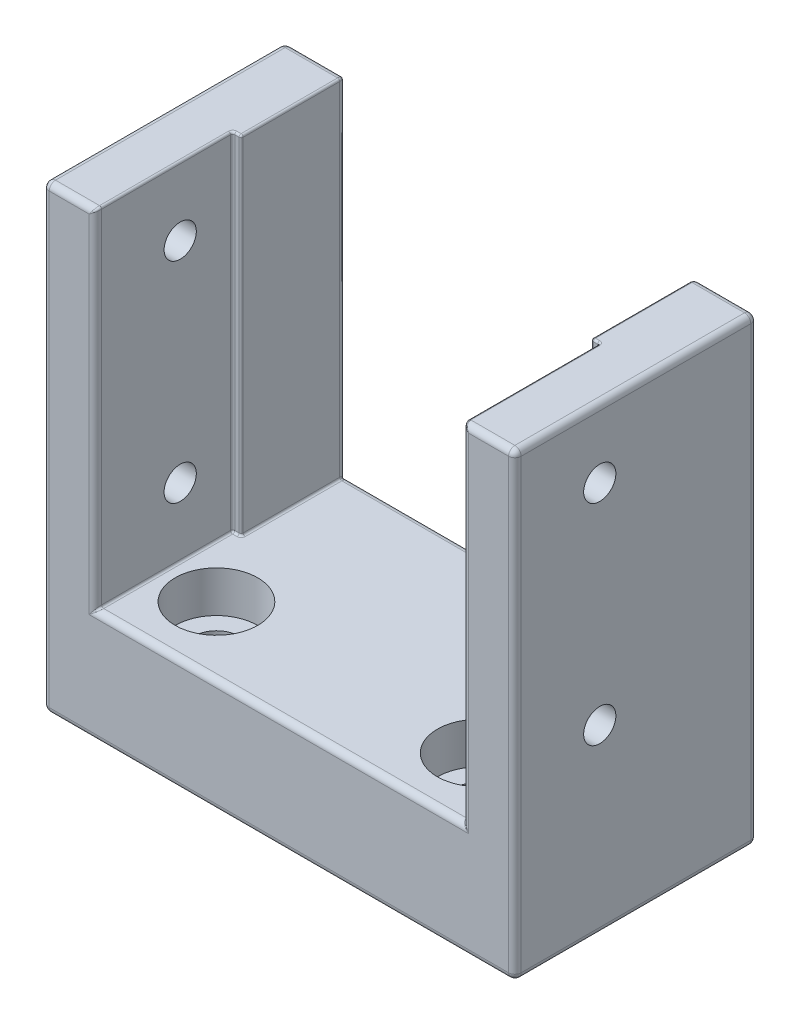
SolidWorks part; units mm, degrees
material "PLA"
ref_plane "Front Plane" through (0, 0, 0) normal (0, 0, 1) x (1, 0, 0)
ref_plane "Top Plane" through (0, 0, 0) normal (0, 1, 0) x (1, 0, 0)
ref_plane "Right Plane" through (0, 0, 0) normal (1, 0, 0) x (0, 0, -1)
sketch "Sketch1" plane through (0, 0, 0) normal (0, 1, 0) x (1, 0, 0)
  line L1 (-22.225, 14.6625) -> (22.225, 14.6625)
  line L2 (-22.225, 14.6625) -> (-22.225, -14.6625)
  line L3 (-22.225, -14.6625) -> (22.225, -14.6625)
  line L4 (22.225, 14.6625) -> (22.225, -14.6625)
  point P4 (0, -14.6625)
  point P6 (-22.225, 0)
  dimension "D1" = 29.325
  dimension "D2" = 44.45
extrude "Boss-Extrude1" add sketch "Sketch1" against normal blind 13.685
sketch "Sketch2" plane through (22.225, 0, 0) normal (1, 0, 0) x (0, 0, -1)
  line L0 (14.6625, -13.685) -> (14.6625, 0) construction
  line L1 (-14.6625, -13.685) -> (14.6625, -13.685)
  line L2 (-14.6625, -13.685) -> (-14.6625, 42)
  line L3 (-14.6625, 42) -> (14.6625, 42)
  line L4 (14.6625, -13.685) -> (14.6625, 42)
  dimension "D1" = 55.685
extrude "Boss-Extrude2" add sketch "Sketch2" along normal blind 6.35
hole_wizard "M3.5 Clearance Hole1" positions "Sketch5" profile "Sketch6" hole size "M3.5" standard "ANSI Metric" end condition through all
sketch "Sketch5" plane through (28.575, 0, 0) normal (1, 0, 0) x (0, 0, -1)
  line L1 (14.6625, 42) -> (-14.6625, 42) construction
  line L2 (-14.6625, 42) -> (-14.6625, -13.685) construction
  point P0 (-4.3875, 33.7)
  point P2 (-4.3875, 8.3)
  dimension "D1" = 10.275
  dimension "D2" = 8.3
  dimension "D3" = 25.4
sketch "Sketch6" plane through (28.575, 33.7, 4.3875) normal (0, 1, 0) x (0, 0, -1)
  line L0 (0, 0) -> (0, 50.8)
  line L1 (0, 50.8) -> (1.95, 50.8)
  line L2 (1.95, 50.8) -> (1.95, 0)
  line L5 (1.95, 0) -> (0, 0)
  line L11 (0, -6.35) -> (0, 107.95) construction
  dimension "Thru Hole Dia." = 3.9
  dimension "Thru Hole Depth" = 50.8
mirror "Mirror1" about plane through (0, 0, 0) normal (1, 0, 0) of "Boss-Extrude2", "M3.5 Clearance Hole1"
sketch "Sketch8" plane through (22.225, 0, 0) normal (-1, 0, 0) x (0, 0, 1)
  line L0 (-14.6625, 42) -> (14.6625, 42) construction
  line L1 (-14.6625, 0) -> (-1.9625, 0)
  line L2 (-14.6625, 0) -> (-14.6625, 42)
  line L3 (-14.6625, 42) -> (-1.9625, 42)
  line L4 (-1.9625, 0) -> (-1.9625, 42)
  dimension "D1" = 12.7
extrude "Boss-Extrude6" add sketch "Sketch8" along normal blind 1.025
mirror "Mirror2" about plane through (0, 0, 0) normal (1, 0, 0) of "Boss-Extrude6"
hole_wizard "CBORE for M5 SHCS1" positions "Sketch9" profile "Sketch10" counterbore size "M5" standard "ANSI Metric" end condition through all
sketch "Sketch9" plane through (0, 0, 0) normal (0, 1, 0) x (1, 0, 0)
  line L0 (-22.225, 1.9625) -> (-22.225, -14.6625) construction
  line L1 (0, -16.1288) -> (0, 16.1288) construction
  point P0 (15.875, -6.35)
  point P2 (-15.875, -6.35)
  point P8 (-22.225, -6.35)
  dimension "D1" = 15.875
  dimension "D2" = 15.875
sketch "Sketch10" plane through (15.875, 0, 6.35) normal (1, 0, 0) x (0, 0, 1)
  line L0 (0, 0) -> (0, 13.685)
  line L1 (0, 13.685) -> (2.75, 13.685)
  line L3 (2.75, 13.685) -> (2.75, 5)
  line L4 (2.75, 5) -> (5, 5)
  line L5 (5, 5) -> (5, 0)
  line L7 (5, 0) -> (0, 0)
  line L11 (0, -6.35) -> (0, 107.95) construction
  dimension "Thru Hole Dia." = 5.5
  dimension "Thru Hole Depth" = 13.685
  dimension "C'Bore Dia." = 10
  dimension "C'Bore Depth" = 5
fillet "Fillet1" radius 0.762 22 edges at (-21.2, 21, -14.6625) (-24.8875, 42, -14.6625) (-28.575, 14.1575, -14.6625) (28.575, 14.1575, -14.6625) (24.8875, 42, -14.6625) (21.2, 21, -14.6625) (0, 0, -14.6625) (22.225, 21, 14.6625) (25.4, 42, 14.6625) (28.575, 14.1575, 14.6625) (-28.575, 14.1575, 14.6625) (-25.4, 42, 14.6625) (-22.225, 21, 14.6625) (0, 0, 14.6625) (28.575, -13.685, 0) (0, -13.685, -14.6625) (-28.575, -13.685, 0) (0, -13.685, 14.6625) (-15.875, -13.685, 9.1) (15.875, -13.685, 9.1) (28.575, 42, 0) (-28.575, 42, 0)
fillet "Fillet2" radius 0.254 24 edges at (-21.4232, -0.2232, -14.4393) (21.4232, -0.2232, -14.4393) (22.4482, 41.7768, 14.4393) (-21.2, 0, -7.9315) (21.2, 0, -7.9315) (22.225, 42, 5.969) (-22.4482, -0.2232, 14.4393) (-21.4232, 41.7768, -14.4393) (-22.4482, 41.7768, 14.4393) (22.4482, -0.2232, 14.4393) (21.4232, 41.7768, -14.4393) (-22.225, 0, 5.969) (-21.7125, 0, -1.9625) (-21.2, 42, -7.9315) (-21.2, 21, -1.9625) (-22.225, 21, -1.9625) (-21.7125, 42, -1.9625) (-22.225, 42, 5.969) (21.7125, 0, -1.9625) (22.225, 0, 5.969) (21.7125, 42, -1.9625) (21.2, 21, -1.9625) (22.225, 21, -1.9625) (21.2, 42, -7.9315)
sketch "Sketch11" plane through (0, 0, 0) normal (0, 1, 0) x (1, 0, 0)
  circle A0 centre (0, 0) radius 4.7455
  dimension "D1" = 9.4909
